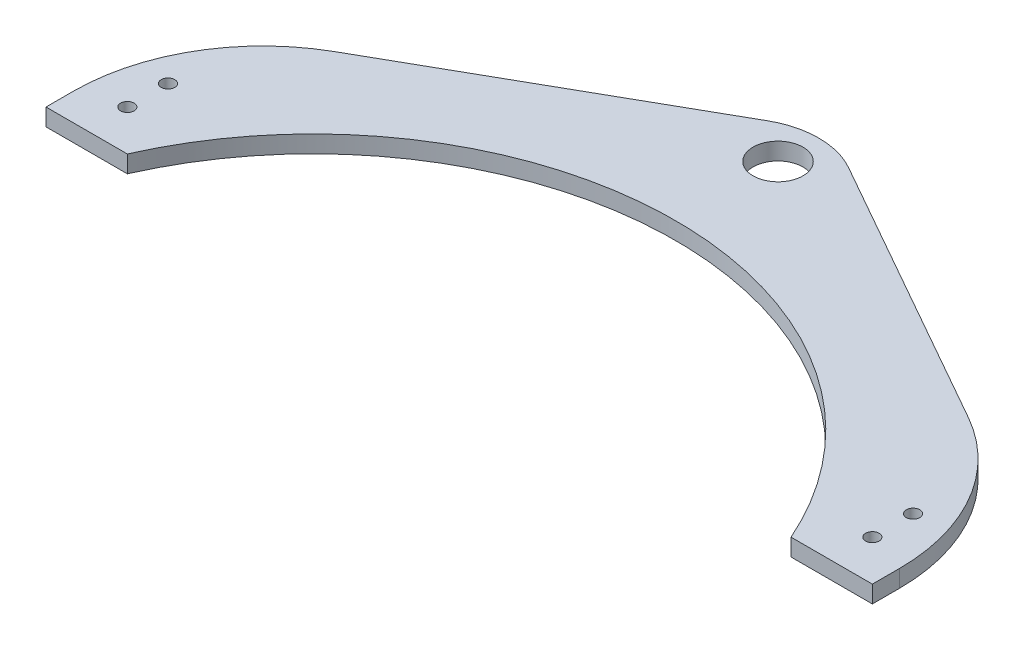
SolidWorks part; units mm, degrees
ref_plane "Front Plane" through (0, 0, 0) normal (0, 0, 1) x (1, 0, 0)
ref_plane "Top Plane" through (0, 0, 0) normal (0, 1, 0) x (1, 0, 0)
ref_plane "Right Plane" through (0, 0, 0) normal (1, 0, 0) x (0, 0, -1)
sketch "Sketch1" plane through (0, 0, 0) normal (0, 1, 0) x (1, 0, 0)
  line L0 (0, 0) -> (122.4, 0)
  line L1 (61.2, 0) -> (61.2, 39.9)
  line L2 (122.4, 0) -> (137.4, 0)
  line L3 (0, 0) -> (-15, 0)
  line L4 (137.4, 0) -> (137.4, 16.6577)
  line L5 (-15, 0) -> (-15, 16.6577)
  line L6 (61.2, 0) -> (61.2, 58.8)
  line L7 (61.2, 58.8) -> (61.2, 66.3)
  line L8 (61.2, 66.3) -> (61.2465, 66.3)
  line L9 (61.2, 66.3) -> (61.1535, 66.3)
  line L10 (68.6399, 64.3514) -> (129.7934, 29.709)
  line L11 (53.7601, 64.3514) -> (-7.3934, 29.709)
  line L12 (129.9, 0) -> (129.9, 7.5)
  line L13 (129.9, 7.5) -> (129.9, 15)
  line L14 (-7.5, 0) -> (-7.5, 15)
  line L15 (119.6512, 35.4544) -> (68.6399, 64.3514)
  line L16 (137.4, 5.0012) -> (137.4, 0)
  line L17 (53.7601, 64.3514) -> (2.7488, 35.4544)
  line L18 (-15, 5.0012) -> (-15, 0)
  arc A0 (0, 0) -> (122.4, 0) centre (61.2, -26.9726) cw
  circle A1 centre (61.2, 58.8) radius 4.6
  arc A2 (61.2465, 66.3) -> (68.6399, 64.3514) centre (61.2465, 51.3) cw
  arc A3 (61.1535, 66.3) -> (53.7601, 64.3514) centre (61.1535, 51.3) ccw
  arc A4 (-15, 16.6577) -> (-7.3934, 29.709) centre (0, 16.6577) cw
  arc A5 (137.4, 16.6577) -> (129.7934, 29.709) centre (122.4, 16.6577) ccw
  circle A6 centre (129.9, 15) radius 1.25
  circle A7 centre (129.9, 7.5) radius 1.25
  circle A8 centre (-7.5, 15) radius 1.25
  circle A9 centre (-7.5, 7.5) radius 1.25
  arc A10 (119.6512, 35.4544) -> (137.4, 5.0012) centre (102.4, 5.0012) cw
  arc A11 (2.7488, 35.4544) -> (-15, 5.0012) centre (20, 5.0012) ccw
  point P17 (65.2, 66.3)
  point P20 (57.2, 66.3)
  point P23 (-15, 25.4)
  point P26 (137.4, 25.4)
  point P41 (137.4, 25.4)
  point P44 (-15, 25.4)
  dimension "D8" = 7.5
  dimension "D11" = 15
  dimension "D12" = 15
  dimension "D15" = 15
  dimension "D16" = 35
  dimension "D1" = 122.4
  dimension "D2" = 39.9
  dimension "D3" = 15
  dimension "D4" = 15
  dimension "D5" = 25.4
  dimension "D6" = 25.4
  dimension "D7" = 58.8
  dimension "D9" = 4
  dimension "D10" = 4
  dimension "D13" = 7.5
  dimension "D14" = 7.5
extrude "Boss-Extrude2" add sketch "Sketch1" along normal blind 3.175 contours L11 A11 L5 L3 A9 A8 A0 L6 A1 L7 L9 A3 | A10 L10 A2 L8 L7 A1 L6 A0 L2 A7 A6 L4 region at (21.7685, 0, -33.4665) region at (100.6315, 0, -33.4665)
